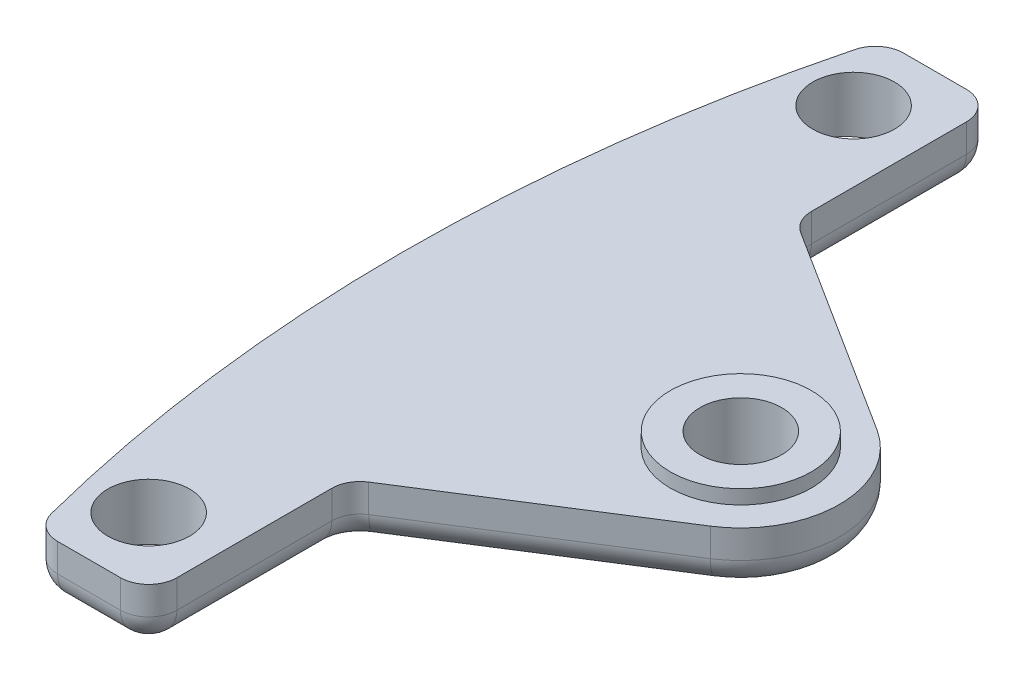
SolidWorks part; units mm, degrees
ref_plane "Спереди" through (0, 0, 0) normal (0, 0, 1) x (1, 0, 0)
ref_plane "Сверху" through (0, 0, 0) normal (0, 1, 0) x (1, 0, 0)
ref_plane "Справа" through (0, 0, 0) normal (1, 0, 0) x (0, 0, -1)
sketch "Эскиз1" plane through (0, 0, 0) normal (0, 1, 0) x (1, 0, 0)
  line L0 (1.8759, 2.9548) -> (-6, 7.9548)
  line L1 (-6, 7.9548) -> (-6, 15)
  line L2 (-6, 15) -> (-10, 15)
  line L3 (-10, 15) -> (-10, -15)
  line L4 (-10, -15) -> (-6, -15)
  line L5 (-6, -15) -> (-6, -7.9548)
  line L6 (-6, -7.9548) -> (1.8759, -2.9548)
  arc A0 (1.8759, -2.9548) -> (1.8759, 2.9548) centre (0, 0) ccw
  circle A1 centre (0, 0) radius 1.45
  dimension "D1" = 2.9
  dimension "D2" = 3.5
  dimension "D3" = 10
  dimension "D4" = 30
  dimension "D5" = 5
  dimension "D6" = 4
extrude "Бобышка-Вытянуть1" add sketch "Эскиз1" along normal blind 2
sketch "Эскиз2" plane through (0, 2, 0) normal (0, 1, 0) x (1, 0, 0)
  circle A0 centre (0, 0) radius 2.5
  circle A1 centre (0, 0) radius 1.45
  dimension "D1" = 2.9
  dimension "D2" = 5
extrude "Бобышка-Вытянуть2" add sketch "Эскиз2" along normal blind 0.5
sketch "Эскиз3" plane through (0, 2, 0) normal (0, 1, 0) x (1, 0, 0)
  line L0 (-6, 15) -> (-10, 15) construction
  line L1 (-10, -15) -> (-6, -15) construction
  line L2 (-8.5, -985) -> (-8.5, 49015) construction
  line L3 (-10, 15) -> (-10, -15) construction
  circle A0 centre (-8.5, 12.5) radius 1.45
  circle A1 centre (-8.5, -12.5) radius 1.45
  dimension "D1" = 2.9
  dimension "D2" = 2.5
  dimension "D3" = 2.5
  dimension "D4" = 1.5
extrude "Вырез-Вытянуть1" cut sketch "Эскиз3" against normal blind 10
sketch "Эскиз4" plane through (0, 2, 0) normal (0, 1, 0) x (1, 0, 0)
  line L0 (-12, -1000) -> (-12, 49000) construction
  line L1 (-10, 15) -> (-10, -15) construction
  line L2 (-10, 15) -> (-10, -15)
  arc A0 (-10, 15) -> (-10, -15) centre (45.25, 0) ccw
  point P8 (-12, 0)
  dimension "D1" = 2
extrude "Бобышка-Вытянуть3" add sketch "Эскиз4" against normal up to surface (2 mm away) up to face at (-8.5, 0, -11.05)
fillet "Скругление1" radius 1 14 edges at (-2.0621, 0, 5.4548) (3.5, 0, 0) (-6, 1, 15) (-6, 0, 11.4774) (-6, 1, 7.9548) (-6, 1, -7.9548) (-2.0621, 0, -5.4548) (-6, 0, -11.4774) (-6, 1, -15) (-10, 1, 15) (-10, 1, -15) (-8, 0, 15) (-8, 0, -15) (-12, 0, 0)
